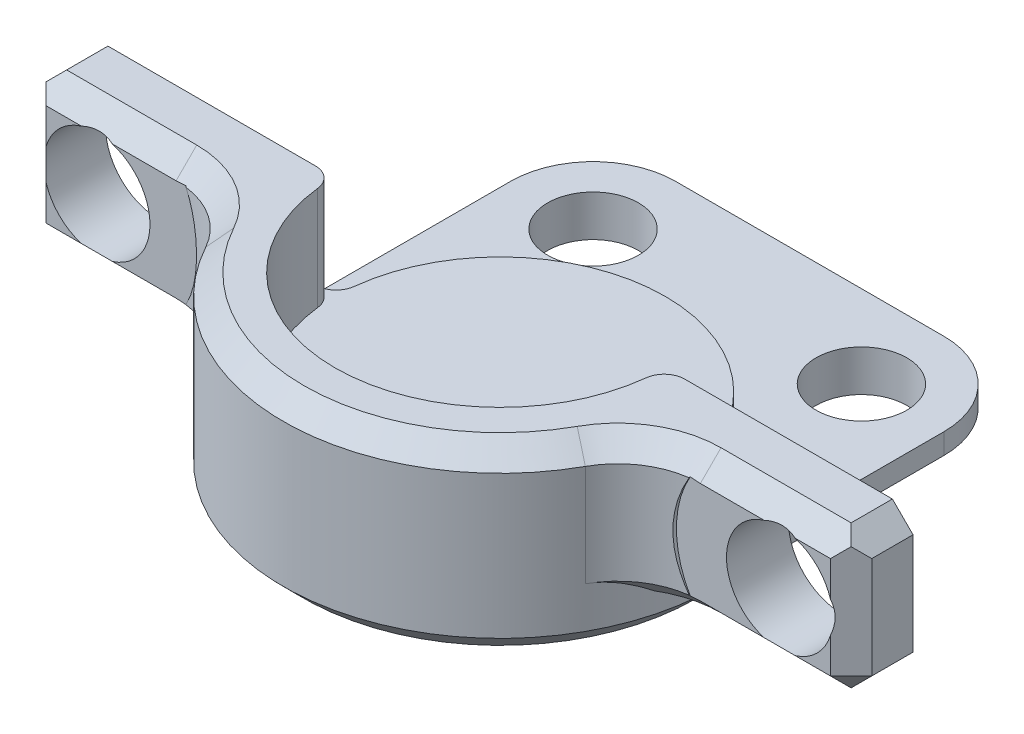
SolidWorks part; units mm, degrees
material "6061 合金"
ref_plane "前视基准面" through (0, 0, 0) normal (0, 0, 1) x (1, 0, 0)
ref_plane "上视基准面" through (0, 0, 0) normal (0, 1, 0) x (1, 0, 0)
ref_plane "右视基准面" through (0, 0, 0) normal (1, 0, 0) x (0, 0, -1)
sketch "草图1" plane through (0, 0, 0) normal (0, 0, 1) x (1, 0, 0)
  line L1 (-20, 4.35) -> (20, 4.35)
  line L2 (-20, 4.35) -> (-20, -2.575)
  line L3 (-20, -2.575) -> (20, -2.575)
  line L4 (20, 4.35) -> (20, -2.575)
extrude "凸台-拉伸1" add sketch "草图1" along normal blind 10.5
sketch "草图2" plane through (0, -2.575, 0) normal (0, -1, 0) x (1, 0, 0)
  circle A0 centre (0, 0) radius 8 construction
  circle A1 centre (0, 0) radius 8
extrude "切除-拉伸1" cut sketch "草图2" against normal blind 10.5
sketch "草图3" plane through (0, -2.575, 0) normal (0, -1, 0) x (1, 0, 0)
  line L1 (-20, 0) -> (-20, 3)
  line L2 (20, 3) -> (13.075, 3)
  line L3 (20, 3) -> (10.0623, 3)
  line L4 (-20, 10.5) -> (-20, 0) construction
  line L5 (20, 0) -> (20, 3)
  line L6 (20, 10.5) -> (20, 0) construction
  line L7 (-10.0623, 3) -> (-20, 3)
  line L8 (-20, 0) -> (-22, 0)
  line L9 (-22, 0) -> (-22, 12)
  line L10 (20, 0) -> (22, 0)
  line L11 (22, 0) -> (22, 12)
  line L12 (22, 12) -> (-22, 12)
  arc A0 (10.0623, 3) -> (-10.0623, 3) centre (0, 0) ccw
  dimension "D1" = 3
extrude "切除-拉伸2" cut sketch "草图3" against normal blind 10.5
fillet "圆角2" radius 4 2 edges at (10.0623, 0.8875, 3) (-10.0623, 0.8875, 3)
sketch "草图5" plane through (0, 0, 3) normal (0, 0, 1) x (1, 0, 0)
  circle A0 centre (16.5375, 0.8875) radius 2.575
  circle A1 centre (-16.5375, 0.8875) radius 2.575
extrude "切除-拉伸3" cut sketch "草图5" against normal blind 10.5
sketch "草图7" plane through (0, -0.65, 0) normal (0, -1, 0) x (1, 0, 0)
  circle A0 centre (0, 0) radius 8
extrude "凸台-拉伸2" add sketch "草图7" along normal up to surface (1.925 mm away)
fillet "圆角3" radius 1 2 edges at (8, -1.6125, 0) (-8, -1.6125, 0)
sketch "草图8" plane through (0, -2.575, 0) normal (0, -1, 0) x (1, 0, 0)
  line L0 (-10.5, 0) -> (-10.5, -15)
  line L1 (-10.5, -15) -> (10.5, -15)
  line L2 (10.5, -15) -> (10.5, 0)
  arc A0 (10.5, 0) -> (-10.5, 0) centre (0, 0) ccw
extrude "凸台-拉伸3" add sketch "草图8" along normal blind 2
fillet "圆角4" radius 4 2 edges at (10.5, -3.575, -15) (-10.5, -3.575, -15)
sketch "草图10" plane through (0, -4.575, 0) normal (0, -1, 0) x (1, 0, 0)
  circle A0 centre (-6.5, -11) radius 2.2
  circle A1 centre (6.5, -11) radius 2.2
extrude "切除-拉伸5" cut sketch "草图10" against normal blind 2
chamfer "倒角2" distance 1 angle 45 19 edges at (20, 0.8875, 3) (-20, 0.8875, 3) (20, -2.575, 1.5) (-20, -2.575, 1.5) (-16.3492, 4.35, 3) (16.3492, 4.35, 3) (-10.6642, 4.35, 3.5559) (10.6642, 4.35, 3.5559) (0, 4.35, 10.5) (0, -4.575, -15) (9.3284, -4.575, -13.8284) (-9.3284, -4.575, -13.8284) (10.5, -4.575, -5.5) (-10.5, -4.575, -5.5) (0, -4.575, 10.5) (10.6642, -2.575, 3.5559) (16.3492, -2.575, 3) (-10.6642, -2.575, 3.5559) (-16.3492, -2.575, 3)
fillet "圆角5" radius 1 2 edges at (8, 1.85, 0) (-8, 1.85, 0)
sketch "草图11" plane through (0, 0, 3) normal (0, 0, 1) x (1, 0, 0)
  circle A0 centre (16.5375, 0.8875) radius 5
  circle A1 centre (-16.5375, 0.8875) radius 5
extrude "切除-拉伸6" cut sketch "草图11" along normal blind 19
chamfer "倒角3" distance 1 angle 45 2 edges at (20, 4.35, 1) (-20, 4.35, 1)
